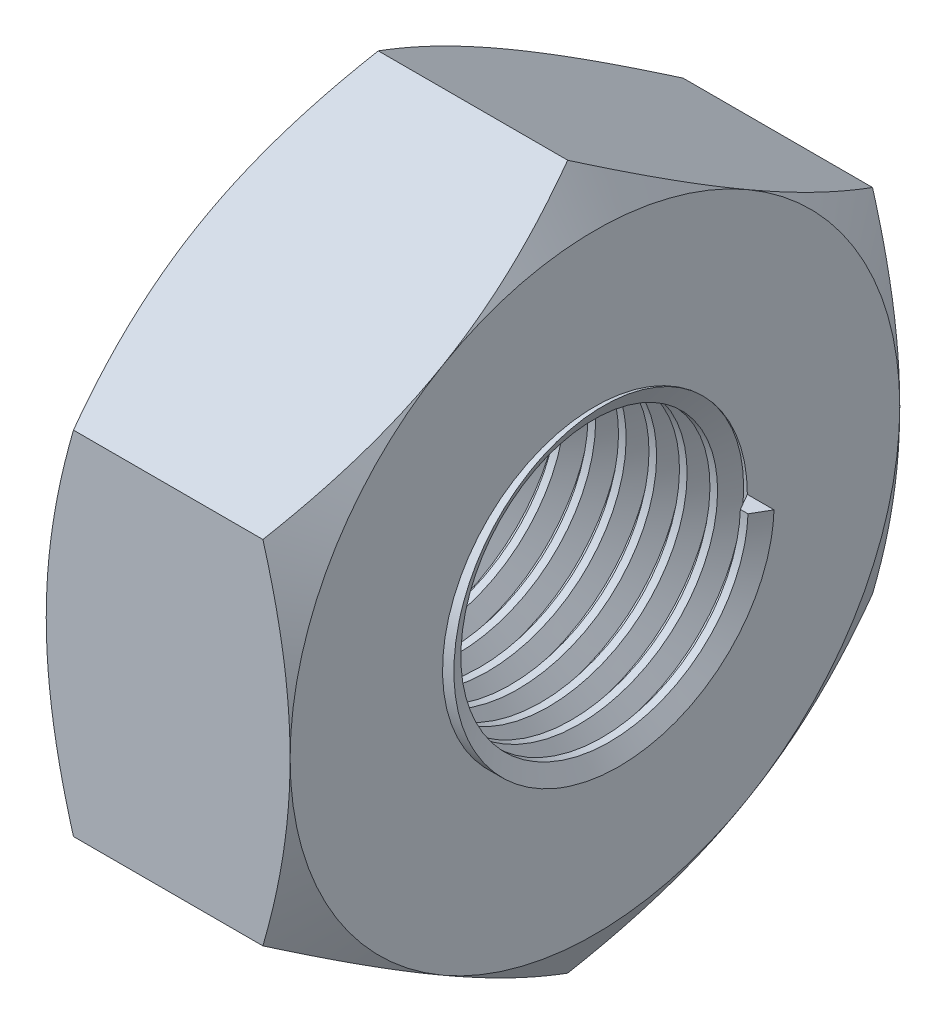
SolidWorks part; units mm, degrees
ref_plane "Front Plane" through (0, 0, 0) normal (0, 0, 1) x (1, 0, 0)
ref_plane "Top Plane" through (0, 0, 0) normal (0, 1, 0) x (1, 0, 0)
ref_plane "Right Plane" through (0, 0, 0) normal (1, 0, 0) x (0, 0, -1)
sketch "Sketch1" plane through (0, 0, 0) normal (1, 0, 0) x (0, 0, -1)
  line L1 (0, 11.547) -> (-10, 5.7735)
  line L2 (-10, 5.7735) -> (-10, -5.7735)
  line L3 (-10, -5.7735) -> (0, -11.547)
  line L4 (0, -11.547) -> (10, -5.7735)
  line L5 (10, -5.7735) -> (10, 5.7735)
  line L6 (10, 5.7735) -> (0, 11.547)
  circle A0 centre (0, 0) radius 10 construction
  circle A1 centre (0, 0) radius 5
  dimension "D1" = 20
extrude "Boss-Extrude1" add sketch "Sketch1" along normal mid plane 8
sketch "Sketch2" plane through (4, 0, 0) normal (1, 0, 0) x (0, 0, -1)
  circle A0 centre (0, 0) radius 10
extrude "Cut-Extrude1" cut sketch "Sketch2" against normal through all draft 60 flip side to cut
mirror "Mirror1" about plane through (0, 0, 0) normal (1, 0, 0) of "Cut-Extrude1"
thread "Thread2" pitch 1 method extrude profile "Thread Profile2" start angle 0, offset 0, length 8, pitch 1, diameter 10
ref_plane "Plane2" through (-4, 0, -5) normal (0, -1, 0) x (0, 0, -1)
sketch "Thread Profile2" plane through (-4, 0, -5) normal (0, -1, 0) x (0, 0, -1)
  line L0 (0, 0) -> (0, 1) construction
  line L11 (0, 0) -> (0, 0.875)
  line L12 (0, 0.875) -> (-0.5413, 0.5625)
  line L13 (-0.5413, 0.5625) -> (-0.5413, 0.3125)
  line L15 (-0.5413, 0.3125) -> (0, 0)
  line L17 (-0.5413, 0.4375) -> (0, 0.4375) construction
  point P2 (0, 0)
  dimension "Pitch" = 1
  dimension "Profile_Angle" = 60
  dimension "Profile_Land" = 0.25
  dimension "Profile_Height" = 0.5413
